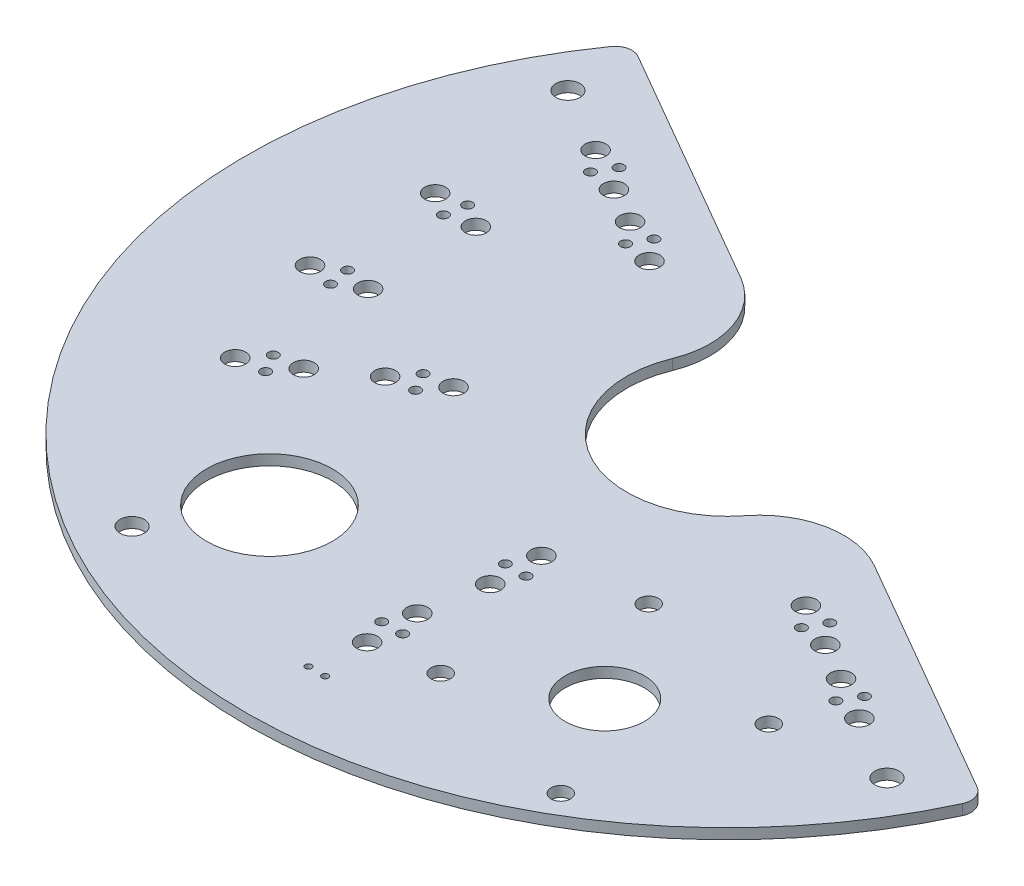
SolidWorks part; units mm, degrees
ref_plane "Front Plane" through (0, 0, 0) normal (0, 0, 1) x (1, 0, 0)
ref_plane "Top Plane" through (0, 0, 0) normal (0, 1, 0) x (1, 0, 0)
ref_plane "Right Plane" through (0, 0, 0) normal (1, 0, 0) x (0, 0, -1)
sketch "Sketch1" plane through (0, 0, 0) normal (0, 1, 0) x (1, 0, 0)
  line L0 (0, 50.8) -> (0, 59.6199) construction
  line L1 (0, 50.8) -> (11.3081, 50.8) construction
  line L2 (0, 0) -> (0, 47) construction
  line L3 (0, 0) -> (-46.286, 8.1615) construction
  line L4 (0, 0) -> (0, 47) construction
  line L5 (0, 0) -> (-46.286, -8.1615) construction
  line L6 (-30.1951, -16.4814) -> (-38.7564, -18.616) construction
  line L7 (1.7716, -33.8648) -> (4.3514, -25.4269) construction
  line L8 (31.2901, -20.38) -> (25.051, -14.141) construction
  line L9 (-31.8057, 17.1605) -> (-38.0448, 23.3996) construction
  circle A0 centre (0, 0) radius 50.8 construction
  circle A1 centre (0, 0) radius 15.24
  circle A2 centre (0, 0) radius 73.025
  circle A3 centre (0, 50.8) radius 6.3 construction
  circle A4 centre (25.4, 43.9941) radius 6.3 construction
  circle A5 centre (43.9941, 25.4) radius 6.3 construction
  circle A6 centre (50.8, 0) radius 6.3 construction
  circle A7 centre (43.9941, -25.4) radius 6.3 construction
  circle A8 centre (25.4, -43.9941) radius 6.3 construction
  circle A9 centre (0, -50.8) radius 6.3 construction
  circle A10 centre (-25.4, -43.9941) radius 6.3 construction
  circle A11 centre (-43.9941, -25.4) radius 6.3 construction
  circle A12 centre (-50.8, 0) radius 6.3 construction
  circle A13 centre (-43.9941, 25.4) radius 6.3 construction
  circle A14 centre (-25.4, 43.9941) radius 6.3 construction
  circle A15 centre (0, 50.8) radius 1.585 construction
  circle A16 centre (-1.585, 50.8) radius 0.75
  circle A17 centre (1.585, 50.8) radius 0.75
  circle A18 centre (0, 50.8) radius 3.8 construction
  circle A19 centre (0, 54.6) radius 1.585
  circle A20 centre (0, 47) radius 1.585
  circle A21 centre (47.285, 27.3) radius 1.585
  circle A22 centre (43.2016, 26.7727) radius 0.75
  circle A23 centre (44.7866, 24.0273) radius 0.75
  circle A24 centre (40.7032, 23.5) radius 1.585
  circle A25 centre (47.285, -27.3) radius 1.585
  circle A26 centre (44.7866, -24.0273) radius 0.75
  circle A27 centre (43.2016, -26.7727) radius 0.75
  circle A28 centre (40.7032, -23.5) radius 1.585
  circle A29 centre (0, -54.6) radius 1.585
  circle A30 centre (1.585, -50.8) radius 0.75
  circle A31 centre (-1.585, -50.8) radius 0.75
  circle A32 centre (0, -47) radius 1.585
  circle A33 centre (-47.285, -27.3) radius 1.585
  circle A34 centre (-43.2016, -26.7727) radius 0.75
  circle A35 centre (-44.7866, -24.0273) radius 0.75
  circle A36 centre (-40.7032, -23.5) radius 1.585
  circle A37 centre (-47.285, 27.3) radius 1.585
  circle A38 centre (-44.7866, 24.0273) radius 0.75
  circle A39 centre (-43.2016, 26.7727) radius 0.75
  circle A40 centre (-40.7032, 23.5) radius 1.585
  circle A41 centre (25.4, 43.9941) radius 20
  circle A42 centre (-25.4, -43.9941) radius 9.525
  circle A43 centre (25.4, -43.9941) radius 6
  circle A44 centre (-46.286, 8.1615) radius 1.585
  circle A45 centre (-50.3035, 7.2604) radius 0.75
  circle A46 centre (-49.753, 10.3822) radius 0.75
  circle A47 centre (-53.7705, 9.4812) radius 1.585
  circle A48 centre (-46.286, -8.1615) radius 1.585
  circle A49 centre (-49.753, -10.3822) radius 0.75
  circle A50 centre (-50.3035, -7.2604) radius 0.75
  circle A51 centre (-53.7705, -9.4812) radius 1.585
  circle A52 centre (-30.191, -16.4817) radius 6.3 construction
  circle A53 centre (-30.191, -16.4817) radius 1.585 construction
  circle A54 centre (-29.3973, -17.8553) radius 0.75
  circle A55 centre (-31.002, -15.1168) radius 0.75
  circle A56 centre (-30.191, -16.4817) radius 3.8 construction
  circle A57 centre (-33.5032, -18.378) radius 1.585
  circle A58 centre (-26.9143, -14.5903) radius 1.585
  circle A59 centre (1.7693, -33.8681) radius 6.3 construction
  circle A60 centre (1.7693, -33.8681) radius 1.585 construction
  circle A61 centre (0.1831, -33.841) radius 0.75
  circle A62 centre (3.3569, -33.8759) radius 0.75
  circle A63 centre (1.7693, -33.8681) radius 3.8 construction
  circle A64 centre (1.8498, -30.0524) radius 1.585
  circle A65 centre (1.7028, -37.651) radius 1.585
  circle A66 centre (31.7545, -18.4007) radius 6.3 construction
  circle A67 centre (31.7545, -18.4007) radius 1.585 construction
  circle A68 centre (30.9859, -19.7885) radius 0.75
  circle A69 centre (32.5067, -17.0026) radius 0.75
  circle A70 centre (31.7545, -18.4007) radius 3.8 construction
  circle A71 centre (28.4231, -16.5382) radius 1.585
  circle A72 centre (35.0633, -20.2353) radius 1.585
  circle A73 centre (-31.9359, 18.6471) radius 6.3 construction
  circle A74 centre (-31.9359, 18.6471) radius 1.585 construction
  circle A75 centre (-32.7045, 17.2593) radius 0.75
  circle A76 centre (-31.1837, 20.0452) radius 0.75
  circle A77 centre (-31.9359, 18.6471) radius 3.8 construction
  circle A78 centre (-35.2672, 20.5095) radius 1.585
  circle A79 centre (-28.627, 16.8125) radius 1.585
  point P50 (0, 0)
  point P84 (0, 0)
  dimension "D1" = 12
  dimension "D2" = 101.6
  dimension "D3" = 3.17
  dimension "D4" = 1.5
  dimension "D5" = 7.6
  dimension "D6" = 6
  dimension "D7" = 3.17
  dimension "D8" = 40
  dimension "D9" = 19.05
  dimension "D10" = 12
  dimension "D11" = 146.05
  dimension "D12" = 30.48
  dimension "D14" = 80
  dimension "D16" = 100
  dimension "D13" = 2
  dimension "D15" = 2
extrude "Boss-Extrude1" add sketch "Sketch1" against normal blind 1.5875
sketch "Sketch2" plane through (0, 0, 0) normal (0, 1, 0) x (1, 0, 0)
  line L0 (0, 0) -> (0, 66.04) construction
  line L1 (0, 0) -> (-57.1923, 33.02) construction
  circle A0 centre (0, 0) radius 66.04 construction
  circle A1 centre (0, 66.04) radius 1.8288 construction
  circle A2 centre (-57.1923, 33.02) radius 1.8288
  circle A3 centre (33.02, 57.1923) radius 1.8288
  circle A4 centre (57.1923, -33.02) radius 1.8288
  circle A5 centre (-33.02, -57.1923) radius 1.8288
  point P17 (0, 0)
  dimension "D1" = 132.08
  dimension "D2" = 3.6576
  dimension "D3" = 2
  dimension "D4" = 60
  dimension "D5" = 4
extrude "Cut-Extrude1" cut sketch "Sketch2" against normal through all
sketch "Sketch3" plane through (0, 0, 0) normal (0, 1, 0) x (1, 0, 0)
  line L0 (-57.1923, 33.02) -> (57.1923, -33.02) construction
  line L1 (-59.5338, 44.6372) -> (68.4238, -29.2392)
  line L2 (-52.7473, 40.719) -> (61.6373, -25.321) construction
  arc A0 (68.4238, -29.2392) -> (-59.5338, 44.6372) centre (0, 0) ccw
  dimension "D1" = 8.89
extrude "Cut-Extrude2" cut sketch "Sketch3" against normal through all
fillet "Fillet1" radius 12.7 2 edges at (15.165, -0.7937, -1.5098) (-6.275, -0.7937, -13.8882)
fillet "Fillet2" radius 2.54 2 edges at (67.2161, -0.7937, 28.542) (-58.3261, -0.7937, -43.9399)
sketch "Sketch4" plane through (0, 0, 0) normal (0, 1, 0) x (1, 0, 0)
  line L0 (0, 0) -> (0, -73.025) construction
  arc A0 (-59.6949, 42.0615) -> (66.2738, -30.6666) centre (0, 0) ccw construction
  circle A1 centre (0, 0) radius 62.23 construction
  circle A2 centre (0, -62.23) radius 0.4953 construction
  circle A3 centre (1.27, -62.23) radius 0.4953
  circle A4 centre (-1.27, -62.23) radius 0.4953
  dimension "D1" = 0.9906
  dimension "D4" = 124.46
  dimension "D2" = 2
  dimension "D3" = 2
extrude "Cut-Extrude3" cut sketch "Sketch4" against normal through all
sketch "Sketch5" plane through (0, -1.5875, 0) normal (0, -1, 0) x (1, 0, 0)
  line L0 (34.4211, 15.231) -> (44.9542, 21.2986)
  line L2 (-30.0652, -20.8147) -> (-29.5513, -21.704)
  line L4 (-43.2679, 43.0512) -> (-27.585, 27.7331)
  line L5 (-41.1598, 45.0708) -> (-25.5353, 29.6313)
  line L6 (-25.6912, 26.743) -> (-24.1699, 25.0755)
  line L7 (-24.4332, 27.897) -> (-22.8858, 26.1617)
  line L8 (-29.8352, -23.5566) -> (-22.3061, -19.4834)
  line L9 (-31.0536, -21.3854) -> (-35.9288, -24.0498)
  line L10 (-29.8352, -23.5566) -> (-36.3971, -27.1309)
  line L11 (-35.9288, -24.0498) -> (-36.5041, -23.022)
  line L12 (-36.3971, -27.1309) -> (-39.4597, -21.5215)
  line L13 (33.3365, 26.1699) -> (41.5359, 31.0198)
  line L14 (28.0125, 9.134) -> (57.7422, 26.2984)
  line L15 (-44.2736, 0.0193) -> (-49.8783, -0.0528)
  line L16 (-41.9942, 2.6626) -> (-49.8102, 2.6011)
  line L29 (46.7892, 22.3211) -> (54.7743, 26.9312)
  line L30 (29.0015, 12.1089) -> (33.4313, 14.6608)
  line L31 (6.096, 41.9407) -> (6.096, 51.4811)
  line L32 (32.4766, 23.8198) -> (40.8902, 28.3377)
  line L33 (-6.096, 38.6381) -> (-6.096, 51.4811)
  line L34 (3.9949, 40.0768) -> (3.9949, 49.6459)
  line L39 (-4.064, 36.8606) -> (-4.1336, 49.6395)
  line L40 (-30.4135, 24.5983) -> (-41.5359, 31.0198)
  line L42 (-29.8903, 21.9498) -> (-41.0294, 28.3377)
  line L93 (-25.0455, -19.0828) -> (-29.5513, -21.704)
  arc A0 (1.2946, 63.4357) -> (1.2454, 61.0243) centre (1.27, 62.23) ccw
  arc A1 (-1.1373, 61.0264) -> (-1.1844, 63.4379) centre (-1.27, 62.23) ccw
  arc A2 (-1.1373, 61.0264) -> (-41.1598, 45.0708) centre (0, 0) ccw
  arc A3 (-1.1844, 63.4379) -> (-56.1144, -29.6131) centre (0, 0) ccw
  arc A4 (54.7743, 26.9312) -> (1.2454, 61.0243) centre (0, 0) ccw
  arc A5 (-43.655, -27.959) -> (-53.8412, -28.7513) centre (-48.9216, -26.1242) cw
  arc A6 (6.096, 51.4811) -> (2.3857, 51.7858) centre (0, 0) ccw
  arc A7 (32.4766, 23.8198) -> (3.9949, 40.0768) centre (0, 0) ccw
  arc A8 (2.3857, 51.7858) -> (2.3071, 49.7553) centre (1.585, 50.8) ccw
  arc A9 (-2.3071, 49.7553) -> (-2.3857, 51.7858) centre (-1.585, 50.8) ccw
  arc A10 (-48.6475, -11.0074) -> (-50.5848, -11.342) centre (-49.753, -10.3822) ccw
  arc A11 (-51.4133, -6.6431) -> (-49.4794, -6.294) centre (-50.3035, -7.2604) ccw
  arc A12 (46.0407, 23.8268) -> (44.1448, 22.9314) centre (44.7866, 24.0273) ccw
  arc A13 (41.9316, 26.7701) -> (43.655, 27.959) centre (43.2016, 26.7727) ccw
  arc A14 (-49.4785, 6.2948) -> (-51.4133, 6.6431) centre (-50.3035, 7.2604) ccw
  arc A15 (-50.5848, 11.342) -> (-48.6465, 11.0056) centre (-49.753, 10.3822) ccw
  arc A16 (57.7422, 26.2984) -> (1.2946, 63.4357) centre (0, 0) ccw
  arc A17 (-2.3857, 51.7858) -> (-6.096, 51.4811) centre (0, 0) ccw
  arc A18 (-2.3071, 49.7553) -> (-4.1336, 49.6395) centre (-0.0696, -0.0032) ccw
  arc A19 (44.9542, 21.2986) -> (44.1448, 22.9314) centre (-0.0696, -0.0032) ccw
  arc A20 (29.0015, 12.1089) -> (-25.0455, -19.0828) centre (2.7445, -4.8151) ccw
  arc A21 (28.0125, 9.134) -> (-22.3061, -19.4834) centre (2.5108, -4.5727) ccw
  arc A22 (46.7892, 22.3211) -> (46.0407, 23.8268) centre (0, 0) ccw
  arc A23 (43.655, 27.959) -> (41.5359, 31.0198) centre (0, 0) ccw
  arc A24 (-46.0407, -23.8268) -> (-44.3342, -22.8406) centre (-44.7866, -24.0273) ccw
  arc A25 (-41.947, -26.9697) -> (-43.655, -27.959) centre (-43.2016, -26.7727) ccw
  arc A26 (41.9316, 26.7701) -> (40.8902, 28.3377) centre (-0.0696, -0.0032) ccw
  circle A27 centre (1.27, 62.23) radius 0.4953
  arc A28 (-43.655, 27.959) -> (-41.9462, 26.9646) centre (-43.2016, 26.7727) ccw
  arc A29 (-44.3301, 22.8422) -> (-46.0407, 23.8268) centre (-44.7866, 24.0273) ccw
  circle A30 centre (-1.27, 62.23) radius 0.4953
  arc A31 (-41.947, -26.9697) -> (-56.1144, -29.6131) centre (-49.4986, -25.7837) cw
  circle A32 centre (-26.7727, 43.2016) radius 1.27 [skipped]
  circle A33 centre (-24.0273, 44.7866) radius 1.27 [skipped]
  circle A34 centre (24.0273, 44.7866) radius 1.27 [skipped]
  circle A35 centre (26.7727, 43.2016) radius 1.27 [skipped]
  circle A36 centre (50.8, 1.585) radius 1.27 [skipped]
  circle A37 centre (50.8, -1.585) radius 1.27 [skipped]
  circle A38 centre (44.7866, -24.0273) radius 1.27 [skipped]
  circle A39 centre (43.2016, -26.7727) radius 1.27 [skipped]
  circle A40 centre (26.7727, -43.2016) radius 1.27 [skipped]
  circle A41 centre (24.0273, -44.7866) radius 1.27 [skipped]
  circle A42 centre (1.585, -50.8) radius 1.27 [skipped]
  circle A43 centre (-1.585, -50.8) radius 1.27 [skipped]
  circle A44 centre (-24.0273, -44.7866) radius 1.27 [skipped]
  circle A45 centre (-26.7727, -43.2016) radius 1.27 [skipped]
  circle A46 centre (-50.8, 1.585) radius 1.27 [skipped]
  circle A47 centre (-50.8, -1.585) radius 1.27 [skipped]
  arc A48 (-39.4597, -21.5215) -> (-44.2736, 0.0193) centre (-4.3951, -2.377) cw
  arc A49 (-41.0294, 28.3377) -> (-41.9462, 26.9646) centre (-0.0696, -0.0032) ccw
  arc A50 (33.3365, 26.1699) -> (6.096, 41.9407) centre (0, 0) ccw
  circle A51 centre (1.585, 50.8) radius 0.75
  arc A52 (-46.0407, 23.8268) -> (-47.6319, 20.4612) centre (0, 0) ccw
  arc A53 (3.9949, 49.6459) -> (2.3071, 49.7553) centre (-0.0696, -0.0032) ccw
  arc A54 (-41.5359, 31.0198) -> (-43.655, 27.959) centre (0, 0) ccw
  arc A55 (-6.096, 38.6381) -> (-25.5353, 29.6313) centre (0, 0) ccw
  arc A56 (-4.064, 36.8606) -> (-24.4332, 27.897) centre (0, 0) ccw
  arc A57 (-44.3301, 22.8422) -> (-48.6465, 11.0056) centre (-0.0696, -0.0032) ccw
  circle A58 centre (-1.585, 50.8) radius 0.75
  circle A59 centre (43.2016, 26.7727) radius 0.75
  arc A60 (-47.6319, 20.4612) -> (-50.5848, 11.342) centre (0, 0) ccw
  arc A61 (-51.4133, 6.6431) -> (-51.4133, -6.6431) centre (0, 0) ccw
  arc A62 (-49.4785, 6.2948) -> (-49.8102, 2.6011) centre (-0.0696, -0.0032) ccw
  circle A63 centre (44.7866, 24.0273) radius 0.75
  arc A64 (-50.5848, -11.342) -> (-46.0407, -23.8268) centre (0, 0) ccw
  arc A65 (-48.6475, -11.0074) -> (-44.3342, -22.8406) centre (-0.0696, -0.0032) ccw
  circle A66 centre (-43.2016, 26.7727) radius 0.75
  circle A67 centre (-44.7866, 24.0273) radius 0.75
  circle A68 centre (-49.753, 10.3822) radius 0.75
  circle A69 centre (-50.3035, 7.2604) radius 0.75
  circle A70 centre (-50.3035, -7.2604) radius 0.75
  circle A71 centre (-49.753, -10.3822) radius 0.75
  circle A72 centre (-44.7866, -24.0273) radius 0.75
  circle A73 centre (-43.2016, -26.7727) radius 0.75
  arc A74 (29.7503, 20.2948) -> (30.8424, 21.1896) centre (30.9918, 19.8934) ccw
  arc A75 (4.5236, 34.6192) -> (30.8424, 21.1896) centre (5.7054, 4.4312) cw
  arc A76 (4.4841, 33.194) -> (29.7503, 20.2948) centre (4.8534, 2.7227) cw
  arc A77 (33.6777, 16.7261) -> (32.7717, 15.8021) centre (32.4444, 17.0292) ccw
  arc A78 (33.4313, 14.6608) -> (32.7717, 15.8021) centre (-10.0197, -9.6891) ccw
  arc A79 (34.4211, 15.231) -> (33.6777, 16.7261) centre (-12.363, -7.1008) ccw
  arc A80 (-0.8928, 32.9745) -> (-0.4432, 34.9562) centre (0.075, 33.7967) ccw
  arc A81 (-29.697, 19.0828) -> (-24.1699, 25.0755) centre (2.1808, -4.7732) cw
  arc A82 (4.5236, 34.6192) -> (4.4841, 33.194) centre (3.4532, 33.9357) ccw
  circle A83 centre (-31.1738, -20.0389) radius 0.75
  arc A84 (-29.697, 19.0828) -> (-28.1584, 17.7555) centre (-29.4254, 17.8422) ccw
  arc A85 (-28.1584, 17.7555) -> (-0.8928, 32.9745) centre (0.881, -2.2367) cw
  arc A86 (-31.3368, 13.0383) -> (-32.985, 14.2011) centre (-31.3367, 14.7878) ccw
  arc A87 (-32.985, 14.2011) -> (-34.3304, 11.6344) centre (112.8254, -63.8668) ccw
  arc A88 (-33.9153, -16.8172) -> (-31.9293, -16.3872) centre (-32.7611, -17.3469) ccw
  arc A89 (-31.9293, -16.3872) -> (-32.6415, -14.9048) centre (-79.0072, -38.0929) ccw
  arc A90 (-30.0652, -20.8147) -> (-31.0536, -21.3854) centre (-31.1268, -20.1175) ccw
  circle A91 centre (-32.7183, -17.2601) radius 0.75
  arc A92 (-34.3304, 11.6344) -> (-33.9153, -16.8172) centre (-7.3644, -2.2011) ccw
  arc A93 (-31.3368, 13.0383) -> (-32.6415, -14.9048) centre (-7.0347, -2.0984) ccw
  circle A94 centre (-31.007, 15.1229) radius 0.75
  circle A95 centre (-29.3984, 17.8491) radius 0.75
  circle A96 centre (0.1843, 33.8387) radius 0.75
  circle A97 centre (3.3549, 33.875) radius 0.75
  circle A98 centre (30.9845, 19.7892) radius 0.75
  circle A99 centre (32.5074, 16.9933) radius 0.75
  arc A100 (-27.585, 27.7331) -> (-30.4135, 24.5983) centre (0, 0) ccw
  arc A101 (-43.2679, 43.0512) -> (-53.8412, -28.7513) centre (0, 0) ccw
  arc A102 (-25.6912, 26.743) -> (-29.8903, 21.9498) centre (0, 0) ccw
  arc A103 (-22.8858, 26.1617) -> (-0.4432, 34.9562) centre (2.1808, -4.7732) cw
  arc A104 (-36.5041, -23.022) -> (-41.9942, 2.6626) centre (2.3103, -1.2963) cw
  arc A105 (-49.8783, -0.0528) -> (-49.4794, -6.294) centre (-0.0696, -0.0032) ccw
  point P141 (0, 0)
  point P142 (0, 0)
  point P149 (0, 0)
  point P150 (0, 0)
  point P151 (-41.9942, 2.6626)
  dimension "D13" = 12
  dimension "D15" = 3
extrude "Boss-Extrude2" add sketch "Sketch5" along normal blind 0.1016
sketch "Sketch6" plane through (0, -1.5875, 0) normal (0, -1, 0) x (1, 0, 0)
  line L0 (0, 0) -> (25.4, 43.9941) construction
  line L1 (25.4, 43.9941) -> (36.5125, 63.2415) construction
  circle A0 centre (25.4, 43.9941) radius 18.1937 construction
  arc A1 (66.2738, 30.6666) -> (-59.6949, -42.0615) centre (0, 0) ccw construction
  circle A2 centre (34.4969, 59.7503) radius 1.4732
  circle A3 centre (9.6438, 53.0909) radius 1.4732
  circle A4 centre (16.3031, 28.2379) radius 1.4732
  circle A5 centre (41.1562, 34.8972) radius 1.4732
  point P20 (25.4, 43.9941)
  dimension "D1" = 2.9464
extrude "Cut-Extrude4" cut sketch "Sketch6" against normal through all
